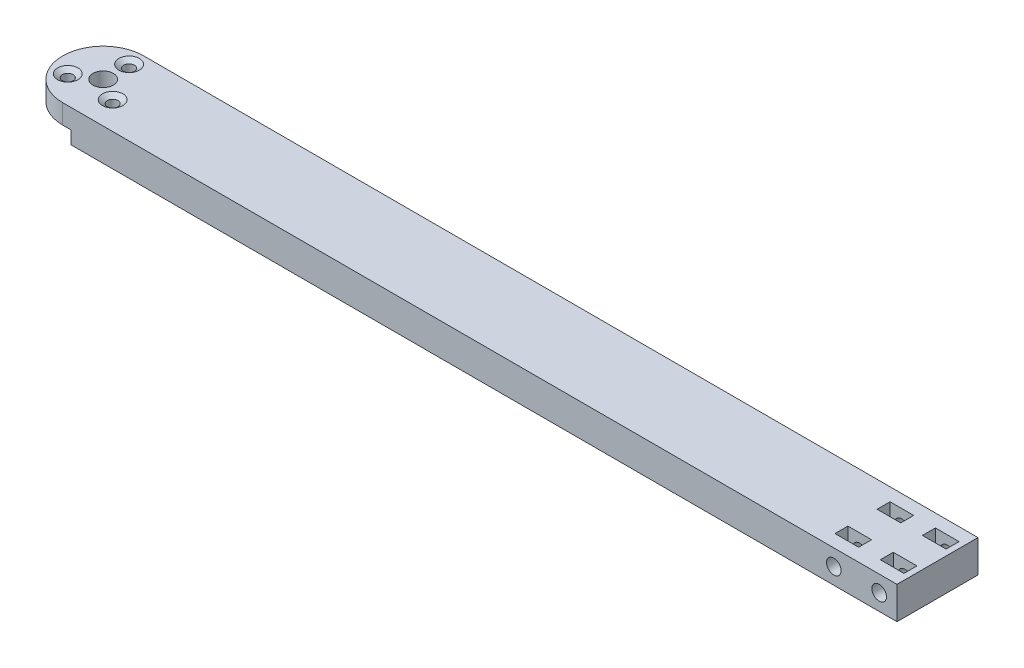
SolidWorks part; units mm, degrees
ref_plane "Front Plane" through (0, 0, 0) normal (0, 0, 1) x (1, 0, 0)
ref_plane "Top Plane" through (0, 0, 0) normal (0, 1, 0) x (1, 0, 0)
ref_plane "Right Plane" through (0, 0, 0) normal (1, 0, 0) x (0, 0, -1)
sketch "Sketch1" plane through (0, 0, 0) normal (0, 1, 0) x (1, 0, 0)
  line L1 (0, 0) -> (270, 0)
  line L2 (0, 0) -> (0, 25)
  line L3 (0, 25) -> (270, 25)
  line L4 (270, 0) -> (270, 25)
  dimension "D1" = 25
  dimension "D2" = 270
extrude "Boss-Extrude1" add sketch "Sketch1" along normal blind 10
sketch "Sketch2" plane through (0, 10, 0) normal (0, 1, 0) x (1, 0, 0)
  line L0 (0, 12.5) -> (270, 12.5) construction
  line L1 (0, 25) -> (0, 0) construction
  line L2 (270, 0) -> (270, 25) construction
  circle A0 centre (12.5, 12.5) radius 3.15
  dimension "D1" = 12.5
  dimension "D2" = 6.3
extrude "Cut-Extrude1" cut sketch "Sketch2" against normal up to next contours A0 | A0 region at (12.5, 10, -12.5)
fillet "Fillet1" radius 12.5 2 edges at (0, 5, 0) (0, 5, -25)
sketch "Sketch3" plane through (0, 0, -25) normal (0, 0, -1) x (-1, 0, 0)
  line L0 (-12.5, 5) -> (-270, 5) construction
  line L1 (-12.5, 0) -> (-12.5, 10) construction
  line L2 (-270, 10) -> (-270, 0) construction
  circle A0 centre (-264.5, 5) radius 2.25
  circle A1 centre (-250.5, 5) radius 2.25
  dimension "D1" = 4.5
  dimension "D2" = 5.5
  dimension "D4" = 14
  dimension "D3" = 2
extrude "Cut-Extrude2" cut sketch "Sketch3" against normal through all
sketch "Sketch5" plane through (0, 10, 0) normal (0, 1, 0) x (1, 0, 0)
  line L0 (264.5, 25) -> (264.5, 0) construction
  line L1 (270, 25) -> (12.5, 25) construction
  line L2 (12.5, 0) -> (270, 0) construction
  line L3 (270, 0) -> (270, 25) construction
  line L4 (264.5, 12.5) -> (270, 12.5) construction
  line L5 (260.85, 17) -> (268.15, 17)
  line L6 (260.85, 17) -> (260.85, 21)
  line L7 (260.85, 21) -> (268.15, 21)
  line L8 (268.15, 17) -> (268.15, 21)
  line L9 (260.85, 17) -> (268.15, 21) construction
  line L10 (260.85, 21) -> (268.15, 17) construction
  line L11 (260.85, 4) -> (268.15, 4)
  line L12 (268.15, 8) -> (268.15, 4)
  line L13 (260.85, 8) -> (268.15, 8)
  line L14 (260.85, 8) -> (260.85, 4)
  line L15 (246.85, 17) -> (246.85, 21)
  line L16 (246.85, 17) -> (254.15, 17)
  line L17 (254.15, 17) -> (254.15, 21)
  line L18 (246.85, 21) -> (254.15, 21)
  line L19 (246.85, 4) -> (254.15, 4)
  line L20 (254.15, 8) -> (254.15, 4)
  line L21 (246.85, 8) -> (254.15, 8)
  line L22 (246.85, 8) -> (246.85, 4)
  point P8 (264.5, 19)
  dimension "D1" = 5.5
  dimension "D2" = 7.3
  dimension "D3" = 4
  dimension "D4" = 6
  dimension "D6" = 14
  dimension "D5" = 2
extrude "Cut-Extrude5" cut sketch "Sketch5" against normal up to next
sketch "Sketch6" plane through (0, 0, 0) normal (0, -1, 0) x (1, 0, 0)
  circle A0 centre (12.5, -12.5) radius 12.75
  dimension "D1" = 25.5
extrude "Cut-Extrude6" cut sketch "Sketch6" against normal blind 4
sketch "Sketch7" plane through (0, 4, 0) normal (0, -1, 0) x (1, 0, 0)
  line L0 (12.5, -12.5) -> (12.5, -20.5) construction
  circle A0 centre (12.5, -20.5) radius 1.65
  circle A1 centre (5.5718, -8.5) radius 1.65
  circle A2 centre (19.4282, -8.5) radius 1.65
  point P10 (12.5, -12.5)
  dimension "D2" = 3.3
  dimension "D4" = 6.9282
  dimension "D5" = 4
  dimension "D1" = 8
  dimension "D3" = 3
extrude "Cut-Extrude7" cut sketch "Sketch7" against normal up to next
chamfer "Chamfer1" distance 1.5 angle 35 3 edges at (12.5, 10, -22.15) (5.5718, 10, -10.15) (19.4282, 10, -10.15) first distance on face at (12.5, 10, -22.15)
